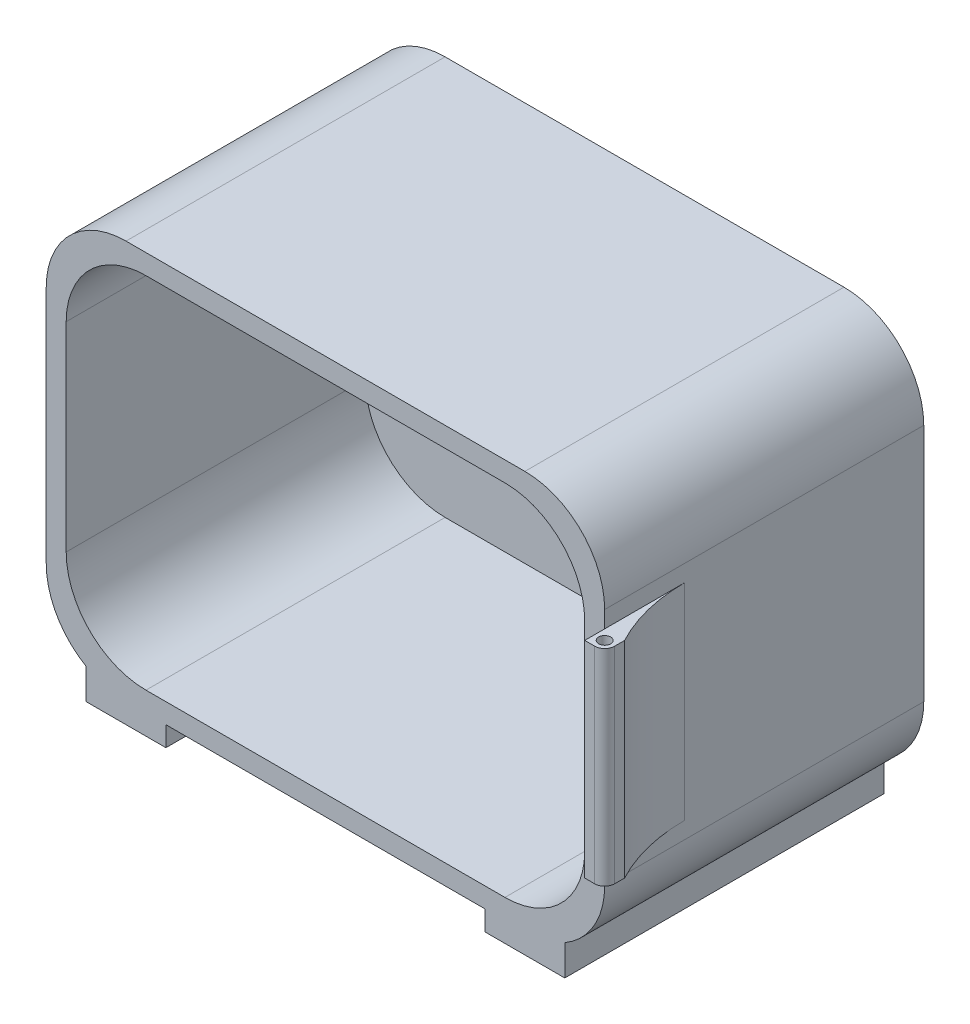
SolidWorks part; units mm, degrees
ref_plane "Front Plane" through (0, 0, 0) normal (0, 0, 1) x (1, 0, 0)
ref_plane "Top Plane" through (0, 0, 0) normal (0, 1, 0) x (1, 0, 0)
ref_plane "Right Plane" through (0, 0, 0) normal (1, 0, 0) x (0, 0, -1)
sketch "Sketch1" plane through (0, 0, 0) normal (0, 0, 1) x (1, 0, 0)
  line L0 (-82.55, 31.75) -> (-82.55, -31.75)
  line L1 (-63.5, 63.5) -> (63.5, 63.5)
  line L2 (-88.9, 38.1) -> (-88.9, -38.1)
  line L3 (-63.5, -63.5) -> (63.5, -63.5)
  line L4 (88.9, 38.1) -> (88.9, -38.1)
  line L5 (-88.9, 63.5) -> (88.9, -63.5) construction
  line L6 (-88.9, -63.5) -> (88.9, 63.5) construction
  line L7 (-57.15, -57.15) -> (57.15, -57.15)
  line L8 (82.55, 31.75) -> (82.55, -31.75)
  line L9 (-57.15, 57.15) -> (57.15, 57.15)
  line L10 (-88.9, 63.5) -> (88.9, 63.5) construction
  line L11 (88.9, 63.5) -> (88.9, -63.5) construction
  line L12 (82.55, 57.15) -> (82.55, -57.15) construction
  line L13 (-82.55, 57.15) -> (82.55, 57.15) construction
  line L14 (-82.55, -57.15) -> (82.55, -57.15) construction
  line L15 (-88.9, -63.5) -> (88.9, -63.5) construction
  line L16 (-82.55, 57.15) -> (-82.55, -57.15) construction
  line L17 (-88.9, 63.5) -> (-88.9, -63.5) construction
  arc A0 (63.5, 63.5) -> (88.9, 38.1) centre (63.5, 38.1) cw
  arc A1 (82.55, 31.75) -> (57.15, 57.15) centre (57.15, 31.75) ccw
  arc A2 (57.15, -57.15) -> (82.55, -31.75) centre (57.15, -31.75) ccw
  arc A3 (63.5, -63.5) -> (88.9, -38.1) centre (63.5, -38.1) ccw
  arc A4 (-82.55, -31.75) -> (-57.15, -57.15) centre (-57.15, -31.75) ccw
  arc A5 (-88.9, -38.1) -> (-63.5, -63.5) centre (-63.5, -38.1) ccw
  arc A6 (-63.5, 63.5) -> (-88.9, 38.1) centre (-63.5, 38.1) ccw
  arc A7 (-82.55, 31.75) -> (-57.15, 57.15) centre (-57.15, 31.75) cw
  point P0 (0, 0)
  dimension "D4" = 25.4
  dimension "D1" = 177.8
  dimension "D2" = 127
  dimension "D3" = 6.35
extrude "Boss-Extrude1" add sketch "Sketch1" against normal blind 95.25
sketch "Sketch2" plane through (0, 0, -95.25) normal (0, 0, -1) x (-1, 0, 0)
  line L0 (-63.5, 63.5) -> (63.5, 63.5)
  line L1 (-63.5, 63.5) -> (63.5, 63.5) construction
  line L2 (0, 63.5) -> (0, -63.5) construction
  line L3 (63.5, -63.5) -> (-63.5, -63.5) construction
  line L4 (63.5, -63.5) -> (-63.5, -63.5)
  line L5 (-88.9, -38.1) -> (-88.9, 38.1) construction
  line L6 (-88.9, -38.1) -> (-88.9, 38.1)
  line L7 (88.9, -38.1) -> (88.9, 38.1)
  arc A0 (-88.9, 38.1) -> (-63.5, 63.5) centre (-63.5, 38.1) cw
  arc A1 (-63.5, -63.5) -> (-88.9, -38.1) centre (-63.5, -38.1) cw
  arc A2 (-88.9, -38.1) -> (-63.5, -63.5) centre (-63.5, -38.1) ccw construction
  arc A3 (63.5, -63.5) -> (88.9, -38.1) centre (63.5, -38.1) ccw
  arc A4 (88.9, 38.1) -> (63.5, 63.5) centre (63.5, 38.1) ccw
extrude "Boss-Extrude2" add sketch "Sketch2" along normal blind 6.35
sketch "Sketch4" plane through (0, -63.5, 0) normal (0, -1, 0) x (1, 0, 0)
  line L0 (-76.2, 0) -> (-50.8, 0)
  line L2 (-76.2, 0) -> (-76.2, -101.6)
  line L3 (-88.9, -101.6) -> (-63.5, -101.6) construction
  line L4 (-76.2, -101.6) -> (-50.8, -101.6)
  line L5 (63.5, -101.6) -> (-63.5, -101.6) construction
  line L6 (-50.8, -101.6) -> (-50.8, 0)
  line L7 (0, 0) -> (0, -101.6) construction
  line L8 (-63.5, 0) -> (63.5, 0) construction
  line L9 (76.2, -101.6) -> (50.8, -101.6)
  line L10 (76.2, 0) -> (76.2, -101.6)
  line L11 (76.2, 0) -> (50.8, 0)
  line L12 (50.8, -101.6) -> (50.8, 0)
  point P4 (-63.5, 0)
  dimension "D1" = 25.4
extrude "Boss-Extrude3" add sketch "Sketch4" along normal blind 6.35 and the other way up to next
sketch "Sketch5" plane through (0, 0, 0) normal (0, 1, 0) x (1, 0, 0)
  line L0 (0, 0) -> (88.9, 0) construction
  line L1 (63.5, 0) -> (-63.5, 0) construction
  line L2 (92.075, 0) -> (95.25, 0) construction
  line L3 (88.9, 25.4) -> (88.9, 0)
  line L4 (92.075, 0) -> (92.075, -3.175) construction
  line L7 (95.25, -6.35) -> (88.9, -6.35)
  line L8 (95.25, -6.35) -> (95.25, 0)
  line L9 (95.25, 0) -> (92.075, 0)
  line L10 (88.9, -6.35) -> (88.9, 0)
  line L11 (95.25, -6.35) -> (88.9, 0) construction
  line L12 (95.25, 0) -> (88.9, -6.35) construction
  line L13 (88.9, -3.175) -> (95.25, -3.175) construction
  arc A3 (95.25, 0) -> (88.9, 25.4) centre (142.875, 25.4) cw
  circle A4 centre (92.075, -3.175) radius 1.905
  point P4 (93.6625, 0)
  point P14 (0, 0)
  point P15 (95.25, 0)
  dimension "D2" = 3.81
  dimension "D1" = 3.175
  dimension "D3" = 88.9
  dimension "D4" = 25.4
extrude "Boss-Extrude5" add sketch "Sketch5" along normal blind 32.766 and the other way blind 32.766 contours A3 L3 L10 L7 L8 A4 region at (91.243, 0, -2.9141)
fillet "Fillet1" radius 3.175 1 edges at (95.25, 0, 6.35)
sketch "Sketch6" plane through (0, 32.766, 0) normal (0, 1, 0) x (1, 0, 0)
  line L0 (90.17, -3.175) -> (88.9, -3.175) construction
  line L1 (88.9, 0) -> (88.9, -6.35) construction
  line L2 (93.98, -3.175) -> (95.25, -3.175) construction
  circle A0 centre (92.075, -3.175) radius 1.905 construction
